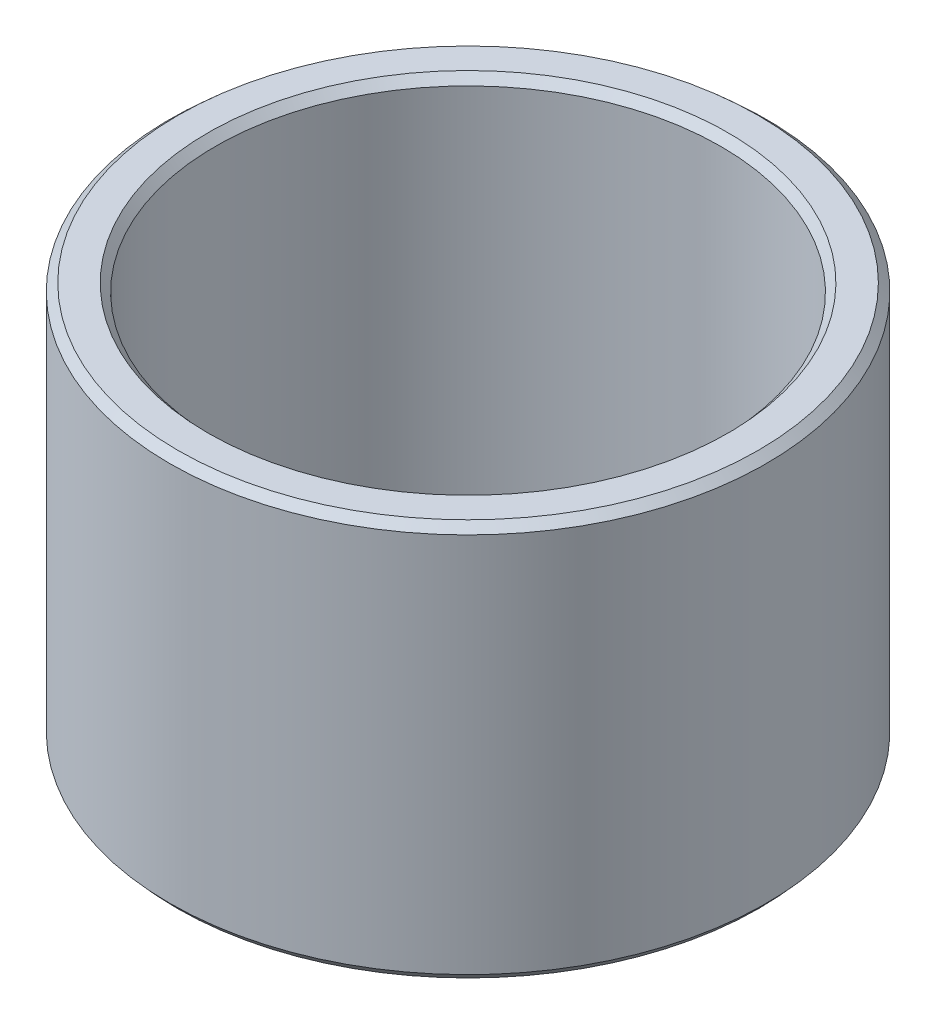
SolidWorks part; units mm, degrees
ref_plane "Front Plane" through (0, 0, 0) normal (0, 0, 1) x (1, 0, 0)
ref_plane "Top Plane" through (0, 0, 0) normal (0, 1, 0) x (1, 0, 0)
ref_plane "Right Plane" through (0, 0, 0) normal (1, 0, 0) x (0, 0, -1)
sketch "Sketch1" plane through (0, 0, 0) normal (0, 1, 0) x (1, 0, 0)
  circle A0 centre (0, 0) radius 50
  dimension "SLEEVE_OD" = 100
extrude "Boss-Extrude1" add sketch "Sketch1" along normal blind 66.431
sketch "Sketch2" plane through (0, 0, 0) normal (0, 1, 0) x (1, 0, 0)
  circle A0 centre (0, 0) radius 42.3697
  dimension "BORE_D" = 84.7394
extrude "Cut-Extrude1" cut sketch "Sketch2" along normal through all
chamfer "Chamfer1" distance 1.2364 angle 47.762 4 edges at (0, 66.431, 42.3697) (0, 0, 42.3697) (0, 0, 50) (0, 66.431, 50) first distance on face at (0, 66.431, 42.3697) first distance on face at (0, 0, 42.3697) first distance on face at (0, 66.431, 50)
